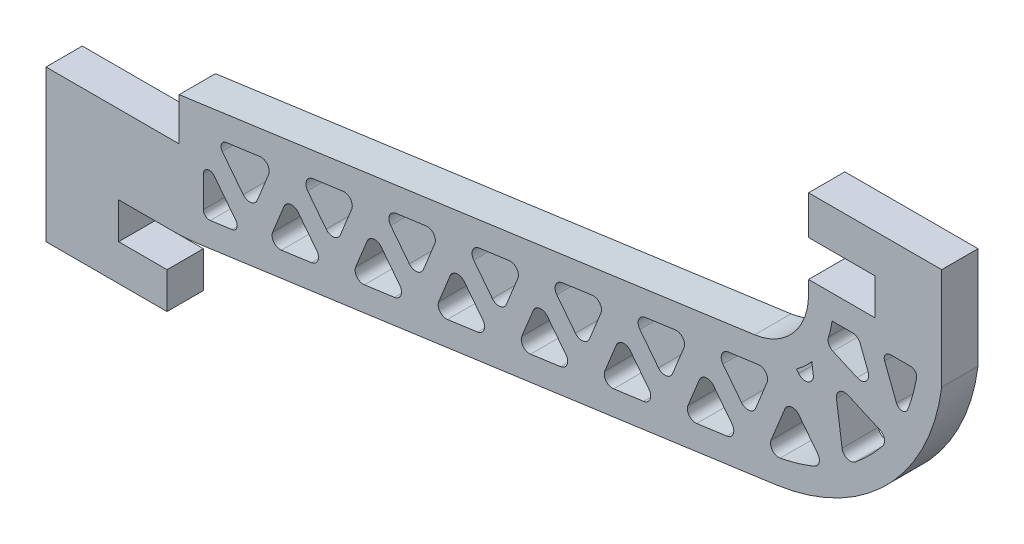
SolidWorks part; units mm, degrees
material "Chipboard"
ref_plane "Front Plane" through (0, 0, 0) normal (0, 0, 1) x (1, 0, 0)
ref_plane "Top Plane" through (0, 0, 0) normal (0, 1, 0) x (1, 0, 0)
ref_plane "Right Plane" through (0, 0, 0) normal (1, 0, 0) x (0, 0, -1)
sketch "Sketch2" plane through (0, 0, 0) normal (0, 0, 1) x (1, 0, 0)
  line L0 (21, 25.7) -> (10, 25.7)
  line L1 (10, 25.7) -> (10, 13.2)
  line L2 (10, 13.2) -> (20, 13.2)
  line L3 (20, 13.2) -> (20, 16.2)
  line L4 (20, 16.2) -> (16, 16.2)
  line L5 (16, 16.2) -> (16, 19.2)
  line L6 (16, 19.2) -> (20.4133, 19.2)
  line L7 (70.3241, 25.9638) -> (22.6096, 19.3515)
  line L8 (84, 39.7939) -> (84, 48.2)
  line L9 (73, 48.2) -> (84, 48.2)
  line L10 (71.3038, 36.2) -> (84, 36.2) construction
  line L14 (73, 48.2) -> (73, 45)
  line L15 (73, 45) -> (78.5, 45)
  line L16 (78.5, 45) -> (78.5, 42)
  line L17 (78.5, 42) -> (73, 42)
  line L18 (73, 42) -> (73, 40.923)
  line L19 (68.5497, 35.8134) -> (21, 29.224)
  line L20 (21, 29.224) -> (21, 25.7)
  line L21 (0, 13.2) -> (0, 80.8979) construction
  line L22 (10, 13.2) -> (0, 13.2) construction
  arc A0 (68.5497, 35.8134) -> (73, 40.923) centre (67.8416, 40.923) ccw
  arc A1 (20.4133, 19.2) -> (22.6096, 19.3515) centre (20.4133, 35.2) ccw
  arc A2 (70.3241, 25.9638) -> (84, 39.7939) centre (68.1278, 41.8123) ccw
  point P8 (68.7549, 50.1919)
  point P10 (20.2621, 7.5888)
  point P24 (62.1548, 57.7044)
  point P26 (13.662, 15.1014)
  dimension "D9" = 3.524
  dimension "D18" = 10
  dimension "D19" = 16
  dimension "D20" = 16
  dimension "D21" = 78.5
  dimension "D1" = 10
  dimension "D2" = 12.5
  dimension "D3" = 21
  dimension "D4" = 16
  dimension "D5" = 20
  dimension "D6" = 3
  dimension "D7" = 16.3
  dimension "D8" = 10
  dimension "D10" = 3
  dimension "D11" = 73
  dimension "D12" = 84
  dimension "D13" = 3
  dimension "D14" = 5.5
  dimension "D15" = 3.2
  dimension "D17" = 12
  dimension "D22" = 1.077
  dimension "D23" = 8.4061
  dimension "D24" = 0.1877
  dimension "D26" = 9.5
extrude "Boss-Extrude1" add sketch "Sketch2" along normal blind 1.5 and the other way blind 1.5
ref_axis "Axis1" through (0, 86.0978, 0) along (0, -1, 0)
sketch "Sketch3" plane through (0, 0, 1.5) normal (0, 0, 1) x (1, 0, 0)
  line L0 (68.8242, 33.8324) -> (66.3664, 33.4918)
  line L1 (23, 24.5599) -> (23, 21.9987)
  line L2 (23, 23.7) -> (12, 23.7)
  line L3 (12, 23.7) -> (12, 15.2)
  line L4 (12, 15.2) -> (14, 15.2)
  line L5 (14, 15.2) -> (14, 15.2)
  line L6 (14, 15.2) -> (14, 15.2)
  line L7 (14, 15.2) -> (14, 21.2)
  line L8 (14, 21.2) -> (20.4133, 21.2)
  line L9 (23.5686, 21.5035) -> (25.3677, 21.7528)
  line L10 (82, 39.9248) -> (82, 46.2)
  line L11 (82, 46.2) -> (80.5, 46.2)
  line L12 (80.5, 46.2) -> (80.5, 46.2)
  line L13 (80.5, 46.2) -> (80.5, 46.2)
  line L14 (80.5, 46.2) -> (80.5, 40)
  line L15 (81.4283, 40) -> (79.7513, 40)
  line L16 (74.9402, 40) -> (74.9402, 40)
  line L17 (21, 29.224) -> (21, 25.7)
  line L18 (21, 25.7) -> (10, 25.7)
  line L19 (10, 25.7) -> (10, 13.2)
  line L20 (10, 13.2) -> (20, 13.2)
  line L21 (20, 13.2) -> (20, 16.2)
  line L22 (20, 16.2) -> (16, 16.2)
  line L23 (16, 16.2) -> (16, 19.2)
  line L24 (16, 19.2) -> (20.4133, 19.2)
  line L25 (22.6096, 19.3515) -> (70.3241, 25.9638)
  line L26 (84, 39.7939) -> (84, 48.2)
  line L27 (84, 48.2) -> (73, 48.2)
  line L28 (73, 48.2) -> (73, 45)
  line L29 (73, 45) -> (78.5, 45)
  line L30 (78.5, 45) -> (78.5, 42)
  line L31 (78.5, 42) -> (73, 42)
  line L32 (73, 42) -> (73, 40.923)
  line L33 (68.5497, 35.8134) -> (21, 29.224)
  line L34 (21, 29.224) -> (21, 25.7)
  line L35 (21, 25.7) -> (10, 25.7)
  line L36 (10, 25.7) -> (10, 13.2)
  line L37 (10, 13.2) -> (20, 13.2)
  line L38 (20, 13.2) -> (20, 16.2)
  line L39 (20, 16.2) -> (16, 16.2)
  line L40 (16, 16.2) -> (16, 19.2)
  line L41 (16, 19.2) -> (20.4133, 19.2)
  line L42 (22.6096, 19.3515) -> (70.3241, 25.9638)
  line L43 (84, 39.7939) -> (84, 48.2)
  line L44 (84, 48.2) -> (73, 48.2)
  line L45 (73, 48.2) -> (73, 45)
  line L46 (73, 45) -> (78.5, 45)
  line L47 (78.5, 45) -> (78.5, 42)
  line L48 (78.5, 42) -> (73, 42)
  line L49 (73, 42) -> (73, 40.923)
  line L50 (68.5497, 35.8134) -> (21, 29.224)
  line L51 (23, 27.482) -> (23, 23.7) construction
  line L52 (80.5, 40) -> (74.9402, 40) construction
  line L53 (23, 27.482) -> (27.2549, 22.0143)
  line L54 (27.2549, 22.0143) -> (29.8626, 28.433)
  line L55 (29.8626, 28.433) -> (34.1175, 22.9653)
  line L56 (34.1175, 22.9653) -> (36.7252, 29.3841)
  line L57 (36.7252, 29.3841) -> (40.9802, 23.9164)
  line L58 (40.9802, 23.9164) -> (43.5879, 30.3351)
  line L59 (43.5879, 30.3351) -> (47.8428, 24.8674)
  line L60 (47.8428, 24.8674) -> (50.4505, 31.2861)
  line L61 (50.4505, 31.2861) -> (54.7054, 25.8184)
  line L62 (54.7054, 25.8184) -> (57.3131, 32.2371)
  line L63 (57.3131, 32.2371) -> (61.568, 26.7695)
  line L64 (61.568, 26.7695) -> (64.1757, 33.1882)
  line L65 (64.1757, 33.1882) -> (68.4306, 27.7205)
  line L66 (68.4306, 27.7205) -> (71.2333, 34.6191)
  line L67 (71.2333, 34.6191) -> (75.0884, 29.6653)
  line L68 (75.0884, 29.6653) -> (74.0275, 37.3206)
  line L69 (74.0275, 37.3206) -> (80.1386, 34.6191)
  line L70 (80.1386, 34.6191) -> (78.0567, 40)
  line L71 (23.8946, 24.867) -> (25.6937, 22.5551)
  line L72 (28.7256, 23.2432) -> (29.6684, 25.5639)
  line L73 (30.8297, 25.7248) -> (32.3681, 23.748)
  line L74 (35.5882, 24.1942) -> (36.531, 26.5149)
  line L75 (37.6924, 26.6758) -> (39.2307, 24.699)
  line L76 (42.4508, 25.1452) -> (43.3937, 27.4659)
  line L77 (44.555, 27.6269) -> (46.0933, 25.65)
  line L78 (49.3135, 26.0963) -> (50.2563, 28.4169)
  line L79 (51.4176, 28.5779) -> (52.956, 26.601)
  line L80 (56.1761, 27.0473) -> (57.1189, 29.368)
  line L81 (58.2802, 29.5289) -> (59.8186, 27.5521)
  line L82 (63.0387, 27.9983) -> (63.9815, 30.319)
  line L83 (65.1428, 30.4799) -> (66.6812, 28.5031)
  line L84 (69.9069, 28.9631) -> (71.0391, 31.7499)
  line L85 (72.2004, 31.9109) -> (73.7529, 29.9159)
  line L86 (81.5033, 33.0318) -> (81.762, 32.9175)
  line L87 (76.2516, 35.3534) -> (78.8732, 34.1945)
  line L88 (81.762, 32.9175) -> (81.6374, 33.2395)
  line L89 (24.5613, 26.9412) -> (26.2878, 24.7226)
  line L90 (27.4491, 24.8835) -> (28.3919, 27.2042)
  line L91 (31.6121, 27.6504) -> (33.1504, 25.6736)
  line L92 (34.3117, 25.8345) -> (35.2546, 28.1552)
  line L93 (38.4747, 28.6014) -> (40.013, 26.6246)
  line L94 (41.1744, 26.7855) -> (42.1172, 29.1062)
  line L95 (45.3373, 29.5525) -> (46.8757, 27.5756)
  line L96 (48.037, 27.7366) -> (48.9798, 30.0573)
  line L97 (52.1999, 30.5035) -> (53.7383, 28.5267)
  line L98 (54.8996, 28.6876) -> (55.8424, 31.0083)
  line L99 (59.0625, 31.4545) -> (60.6009, 29.4777)
  line L100 (61.7622, 29.6386) -> (62.705, 31.9593)
  line L101 (65.9252, 32.4056) -> (67.4635, 30.4287)
  line L102 (68.6248, 30.5897) -> (69.5677, 32.9104)
  line L103 (72.0015, 35.0974) -> (72.1844, 34.8625)
  line L104 (73.3891, 35.3711) -> (73.2668, 36.253)
  line L105 (75.015, 37.8681) -> (77.0205, 36.9815)
  line L106 (77.9255, 37.8449) -> (77.2591, 39.5673)
  line L107 (29.4456, 22.3179) -> (31.9268, 22.6618)
  line L108 (22.2897, 26.9293) -> (27.502, 20.2314) construction
  line L109 (27.502, 20.2314) -> (30.1097, 26.6501) construction
  line L110 (27.6719, 28.1294) -> (24.8872, 27.7435)
  line L111 (22.3351, 21.3325) -> (70.0496, 27.9448) construction
  line L112 (23.7103, 28.0347) -> (27.0078, 23.7973) construction
  line L113 (36.3083, 23.2689) -> (38.7894, 23.6128)
  line L114 (68.8242, 33.8324) -> (23, 27.482) construction
  line L115 (27.0078, 23.7973) -> (29.6155, 30.216) construction
  line L116 (29.6155, 30.216) -> (33.8705, 24.7483) construction
  line L117 (30.1097, 26.6501) -> (34.3646, 21.1824) construction
  line L118 (34.5345, 29.0805) -> (32.0533, 28.7366)
  line L119 (34.3646, 21.1824) -> (36.9723, 27.6011) construction
  line L120 (33.8705, 24.7483) -> (36.4782, 31.167) construction
  line L121 (36.4782, 31.167) -> (40.7331, 25.6993) construction
  line L122 (43.1709, 24.22) -> (45.6521, 24.5638)
  line L123 (36.9723, 27.6011) -> (41.2272, 22.1334) construction
  line L124 (41.3971, 30.0315) -> (38.916, 29.6877)
  line L125 (41.2272, 22.1334) -> (43.8349, 28.5521) construction
  line L126 (40.7331, 25.6993) -> (43.3408, 32.1181) construction
  line L127 (43.3408, 32.1181) -> (47.5957, 26.6504) construction
  line L128 (50.0335, 25.171) -> (52.5147, 25.5148)
  line L129 (43.8349, 28.5521) -> (48.0899, 23.0844) construction
  line L130 (48.2598, 30.9825) -> (45.7786, 30.6387)
  line L131 (48.0899, 23.0844) -> (50.6976, 29.5032) construction
  line L132 (56.8961, 26.122) -> (59.3773, 26.4659)
  line L133 (47.5957, 26.6504) -> (50.2034, 33.0691) construction
  line L134 (50.2034, 33.0691) -> (54.4583, 27.6014) construction
  line L135 (50.6976, 29.5032) -> (54.9525, 24.0355) construction
  line L136 (63.7587, 27.073) -> (66.2399, 27.4169)
  line L137 (54.9525, 24.0355) -> (57.5602, 30.4542) construction
  line L138 (57.5602, 30.4542) -> (61.8151, 24.9865) construction
  line L139 (55.1224, 31.9336) -> (52.6412, 31.5897)
  line L140 (61.8151, 24.9865) -> (64.4228, 31.4052) construction
  line L141 (54.4583, 27.6014) -> (57.066, 34.0201) construction
  line L142 (57.066, 34.0201) -> (61.3209, 28.5524) construction
  line L143 (61.985, 32.8846) -> (59.5038, 32.5407)
  line L144 (61.3209, 28.5524) -> (63.9286, 34.9711) construction
  line L145 (63.9286, 34.9711) -> (68.1836, 29.5034) construction
  line L146 (69.46, 27.8631) -> (70.0496, 27.9448)
  line L147 (64.4228, 31.4052) -> (68.6777, 25.9375) construction
  line L148 (68.6777, 25.9375) -> (71.4804, 32.8362) construction
  line L149 (73.7358, 32.8688) -> (72.9143, 38.7967) construction
  line L150 (68.1836, 29.5034) -> (70.9862, 36.4021) construction
  line L151 (70.9862, 36.4021) -> (73.7358, 32.8688) construction
  line L152 (75.7694, 31.3072) -> (75.3074, 34.6414)
  line L153 (71.4804, 32.8362) -> (76.4409, 26.4618) construction
  line L154 (72.9143, 38.7967) -> (78.5152, 36.3208) construction
  line L155 (76.4409, 26.4618) -> (75.1407, 35.8445) construction
  line L156 (80.2635, 36.7904) -> (79.285, 39.3196)
  line L157 (75.1407, 35.8445) -> (81.762, 32.9175) construction
  line L158 (78.5152, 36.3208) -> (77.2173, 39.6752) construction
  line L159 (81.762, 32.9175) -> (78.896, 40.3248) construction
  line L160 (76.6278, 40) -> (74.9402, 40)
  arc A0 (20.4133, 21.2) -> (22.3351, 21.3325) centre (20.4133, 35.2) ccw
  arc A1 (70.6563, 28.0425) -> (73.4773, 28.8747) centre (68.1278, 41.8123) ccw
  arc A2 (68.8242, 33.8324) -> (68.8456, 33.8354) centre (67.8416, 40.923) ccw
  arc A3 (20.4133, 19.2) -> (22.6096, 19.3515) centre (20.4133, 35.2) ccw
  arc A4 (70.3241, 25.9638) -> (84, 39.7939) centre (68.1278, 41.8123) ccw
  arc A5 (68.5497, 35.8134) -> (73, 40.923) centre (67.8416, 40.923) ccw
  arc A6 (20.4133, 19.2) -> (22.6096, 19.3515) centre (20.4133, 35.2) ccw
  arc A7 (70.3241, 25.9638) -> (84, 39.7939) centre (68.1278, 41.8123) ccw
  arc A8 (68.5497, 35.8134) -> (73, 40.923) centre (67.8416, 40.923) ccw
  arc A9 (72.0015, 35.0974) -> (73.2668, 36.253) centre (67.8416, 40.923) ccw
  arc A10 (76.8622, 30.8711) -> (79.1316, 33.1569) centre (68.1278, 41.8123) ccw
  arc A11 (68.8242, 33.8324) -> (74.9402, 40) centre (67.8416, 40.923) ccw construction
  arc A12 (74.6453, 38.6976) -> (74.9402, 40) centre (67.8416, 40.923) ccw
  arc A13 (70.0496, 27.9448) -> (82, 39.9248) centre (68.1278, 41.8123) ccw construction
  arc A14 (81.1966, 36.7915) -> (81.9209, 39.4144) centre (68.1278, 41.8123) ccw
  arc A15 (23.8946, 24.867) -> (23, 24.5599) centre (23.5, 24.5599) ccw
  arc A16 (23, 21.9987) -> (23.5686, 21.5035) centre (23.5, 21.9987) ccw
  arc A17 (25.3677, 21.7528) -> (25.6937, 22.5551) centre (25.2991, 22.2481) ccw
  arc A18 (24.8872, 27.7435) -> (24.5613, 26.9412) centre (24.9559, 27.2483) ccw
  arc A19 (26.2878, 24.7226) -> (27.4491, 24.8835) centre (26.822, 25.1383) ccw
  arc A20 (28.3919, 27.2042) -> (27.6719, 28.1294) centre (27.7648, 27.4589) ccw
  arc A21 (29.6684, 25.5639) -> (30.8297, 25.7248) centre (30.2955, 25.3091) cw
  arc A22 (32.3681, 23.748) -> (31.9268, 22.6618) centre (31.8339, 23.3322) cw
  arc A23 (29.4456, 22.3179) -> (28.7256, 23.2432) centre (29.3527, 22.9884) cw
  arc A24 (33.1504, 25.6736) -> (34.3117, 25.8345) centre (33.6846, 26.0893) ccw
  arc A25 (35.2546, 28.1552) -> (34.5345, 29.0805) centre (34.6274, 28.41) ccw
  arc A26 (32.0533, 28.7366) -> (31.6121, 27.6504) centre (32.1463, 28.0661) ccw
  arc A27 (40.013, 26.6246) -> (41.1744, 26.7855) centre (40.5472, 27.0403) ccw
  arc A28 (42.1172, 29.1062) -> (41.3971, 30.0315) centre (41.4901, 29.361) ccw
  arc A29 (38.916, 29.6877) -> (38.4747, 28.6014) centre (39.0089, 29.0172) ccw
  arc A30 (39.2307, 24.699) -> (38.7894, 23.6128) centre (38.6965, 24.2833) cw
  arc A31 (36.3083, 23.2689) -> (35.5882, 24.1942) centre (36.2153, 23.9394) cw
  arc A32 (36.531, 26.5149) -> (37.6924, 26.6758) centre (37.1582, 26.2601) cw
  arc A33 (43.3937, 27.4659) -> (44.555, 27.6269) centre (44.0208, 27.2111) cw
  arc A34 (46.0933, 25.65) -> (45.6521, 24.5638) centre (45.5591, 25.2343) cw
  arc A35 (43.1709, 24.22) -> (42.4508, 25.1452) centre (43.078, 24.8905) cw
  arc A36 (46.8757, 27.5756) -> (48.037, 27.7366) centre (47.4099, 27.9913) ccw
  arc A37 (48.9798, 30.0573) -> (48.2598, 30.9825) centre (48.3527, 30.312) ccw
  arc A38 (45.7786, 30.6387) -> (45.3373, 29.5525) centre (45.8715, 29.9682) ccw
  arc A39 (50.2563, 28.4169) -> (51.4176, 28.5779) centre (50.8834, 28.1622) cw
  arc A40 (52.956, 26.601) -> (52.5147, 25.5148) centre (52.4218, 26.1853) cw
  arc A41 (50.0335, 25.171) -> (49.3135, 26.0963) centre (49.9406, 25.8415) cw
  arc A42 (53.7383, 28.5267) -> (54.8996, 28.6876) centre (54.2725, 28.9424) ccw
  arc A43 (55.8424, 31.0083) -> (55.1224, 31.9336) centre (55.2153, 31.2631) ccw
  arc A44 (52.6412, 31.5897) -> (52.1999, 30.5035) centre (52.7341, 30.9192) ccw
  arc A45 (58.2802, 29.5289) -> (57.1189, 29.368) centre (57.746, 29.1132) ccw
  arc A46 (56.1761, 27.0473) -> (56.8961, 26.122) centre (56.8032, 26.7925) ccw
  arc A47 (59.3773, 26.4659) -> (59.8186, 27.5521) centre (59.2844, 27.1364) ccw
  arc A48 (60.6009, 29.4777) -> (61.7622, 29.6386) centre (61.1351, 29.8934) ccw
  arc A49 (62.705, 31.9593) -> (61.985, 32.8846) centre (62.0779, 32.2141) ccw
  arc A50 (59.5038, 32.5407) -> (59.0625, 31.4545) centre (59.5967, 31.8702) ccw
  arc A51 (63.9815, 30.319) -> (65.1428, 30.4799) centre (64.6086, 30.0642) cw
  arc A52 (66.6812, 28.5031) -> (66.2399, 27.4169) centre (66.147, 28.0874) cw
  arc A53 (63.7587, 27.073) -> (63.0387, 27.9983) centre (63.6658, 27.7435) cw
  arc A54 (67.4635, 30.4287) -> (68.6248, 30.5897) centre (67.9977, 30.8444) ccw
  arc A55 (69.5677, 32.9104) -> (68.8456, 33.8354) centre (68.9405, 33.1651) ccw
  arc A56 (66.3664, 33.4918) -> (65.9252, 32.4056) centre (66.4594, 32.8213) ccw
  arc A57 (71.0391, 31.7499) -> (72.2004, 31.9109) centre (71.6662, 31.4952) cw
  arc A58 (73.7529, 29.9159) -> (73.4773, 28.8747) centre (73.2187, 29.5002) cw
  arc A59 (70.6563, 28.0425) -> (69.9069, 28.9631) centre (70.534, 28.7083) cw
  arc A60 (75.3074, 34.6414) -> (76.2516, 35.3534) centre (75.9779, 34.7343) cw
  arc A61 (78.8732, 34.1945) -> (79.1316, 33.1569) centre (78.5996, 33.5753) cw
  arc A62 (76.8622, 30.8711) -> (75.7694, 31.3072) centre (76.4399, 31.4001) cw
  arc A63 (73.3891, 35.3711) -> (72.1844, 34.8625) centre (72.7186, 35.2782) cw
  arc A64 (77.0205, 36.9815) -> (77.9255, 37.8449) centre (77.2942, 37.6006) ccw
  arc A65 (77.2591, 39.5673) -> (76.6278, 40) centre (76.6278, 39.3231) ccw
  arc A66 (74.6453, 38.6976) -> (75.015, 37.8681) centre (75.2887, 38.4872) ccw
  arc A67 (80.2635, 36.7904) -> (81.1966, 36.7915) centre (80.7298, 36.9708) ccw
  arc A68 (81.9209, 39.4144) -> (81.4283, 40) centre (81.4283, 39.5) ccw
  arc A69 (79.7513, 40) -> (79.285, 39.3196) centre (79.7513, 39.5) ccw
  point P164 (28.2843, 22.157)
  point P170 (35.6958, 29.2414)
  point P178 (42.5585, 30.1924)
  point P214 (56.2837, 32.0945)
  point P229 (63.1463, 33.0455)
  point P269 (77.0917, 40)
  point P274 (80.7021, 35.6569)
  dimension "D7" = 0.5
  dimension "D8" = 0.5
  dimension "D9" = 0.6769
  dimension "D10" = 0.6769
  dimension "D11" = 0.6769
  dimension "D12" = 0.6769
  dimension "D13" = 0.6769
  dimension "D14" = 0.6769
  dimension "D15" = 0.6769
  dimension "D16" = 0.6769
  dimension "D17" = 0.6769
  dimension "D18" = 0.6769
  dimension "D19" = 0.6769
  dimension "D20" = 0.6769
  dimension "D21" = 0.6769
  dimension "D22" = 0.6769
  dimension "D23" = 0.6769
  dimension "D24" = 0.6769
  dimension "D25" = 0.6769
  dimension "D26" = 0.5
  dimension "D3" = 60
  dimension "D4" = 60
  dimension "D1" = 0
  dimension "D2" = 2
  dimension "D5" = 0.9
  dimension "D6" = 0.9
extrude "Cut-Extrude1" cut sketch "Sketch3" against normal through all contours L9 A17 L71 A15 L1 A16 | L90 A20 L110 A18 L89 A19 | A23 L107 A22 L73 A21 L72 | L118 A26 L91 A24 L92 A25 | A32 L74 A31 L113 A30 L75 | L124 A29 L93 A27 L94 A28 | A35 L122 A34 L77 A33 L76 | L130 A38 L95 A36 L96 A37 | A41 L128 A40 L79 A39 L78 | L139 A44 L97 A42 L98 A43 | L132 A47 L81 A45 L80 A46 | L143 A50 L99 A48 L100 A49 | A53 L136 A52 L83 A51 L82 | L0 A56 L101 A54 L102 A55 A2 | A59 A1 A58 L85 A57 L84 | A62 A10 A61 L87 A60 L152 | A63 L104 A9 L103 | A12 A66 L105 A64 L106 A65 L160 | L15 A69 L156 A67 A14 A68 region at (67.7992, 32.2769, 1.5) region at (24.0913, 23.0115, 1.5) region at (80.6532, 38.5634, 1.5) region at (30.4941, 23.8766, 1.5) region at (37.3567, 24.8276, 1.5) region at (44.2193, 25.7786, 1.5) region at (51.0819, 26.7297, 1.5) region at (57.9445, 27.6807, 1.5) region at (64.8072, 28.6317, 1.5) region at (71.7806, 29.8711, 1.5) region at (76.9981, 33.1995, 1.5) region at (26.5933, 26.583, 1.5) region at (33.4861, 27.5218, 1.5) region at (40.3487, 28.4728, 1.5) region at (47.2113, 29.4239, 1.5) region at (54.074, 30.3749, 1.5) region at (60.9366, 31.3259, 1.5) region at (72.8355, 35.2461, 1.5) region at (76.3034, 38.5554, 1.5)
